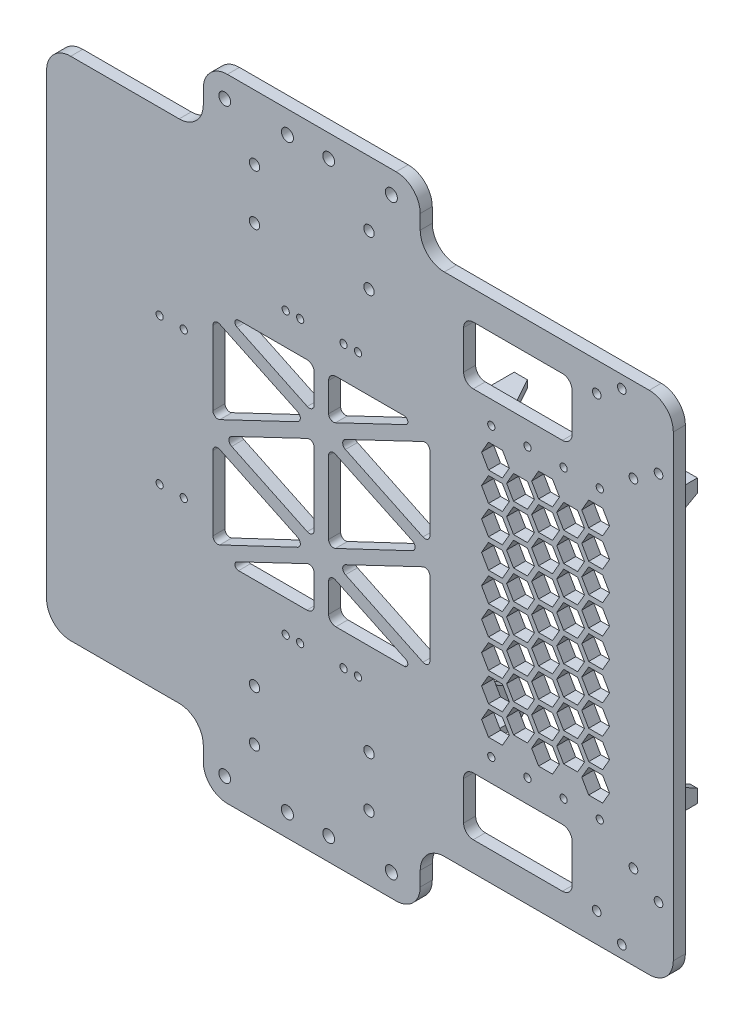
SolidWorks part; units mm, degrees
ref_plane "前视基准面" through (0, 0, 0) normal (0, 0, 1) x (1, 0, 0)
ref_plane "上视基准面" through (0, 0, 0) normal (0, 1, 0) x (1, 0, 0)
ref_plane "右视基准面" through (0, 0, 0) normal (1, 0, 0) x (0, 0, -1)
sketch "草图1" plane through (0, 0, 0) normal (0, 0, 1) x (1, 0, 0)
  line L2 (-130, 95) -> (-130, -95)
  line L3 (-120, -105) -> (-75, -105)
  line L4 (130, 95) -> (130, -95)
  line L5 (126.7518, 102.3765) -> (130, 105) construction
  line L6 (-130, -105) -> (-126.7518, -102.3765) construction
  line L9 (-65, -115) -> (-65, -121)
  line L10 (-55, -131) -> (15, -131)
  line L11 (25, -121) -> (25, -115)
  line L13 (35, -105) -> (120, -105)
  line L14 (126.7518, -102.3765) -> (130, -105) construction
  line L15 (-130, 105) -> (-126.7518, 102.3765) construction
  line L16 (-130, 0) -> (130, 0) construction
  line L17 (35, 105) -> (120, 105)
  line L18 (25, 121) -> (25, 115)
  line L19 (-55, 131) -> (15, 131)
  line L20 (-65, 115) -> (-65, 121)
  line L21 (-120, 105) -> (-75, 105)
  arc A1 (-120, -105) -> (-130, -95) centre (-120, -95) cw
  arc A3 (120, -105) -> (130, -95) centre (120, -95) ccw
  arc A8 (-65, -115) -> (-75, -105) centre (-75, -115) ccw
  arc A9 (25, -115) -> (35, -105) centre (35, -115) cw
  arc A10 (-55, -131) -> (-65, -121) centre (-55, -121) cw
  arc A11 (15, -131) -> (25, -121) centre (15, -121) ccw
  arc A12 (15, 131) -> (25, 121) centre (15, 121) cw
  arc A13 (-55, 131) -> (-65, 121) centre (-55, 121) ccw
  arc A14 (25, 115) -> (35, 105) centre (35, 115) ccw
  arc A15 (-65, 115) -> (-75, 105) centre (-75, 115) cw
  arc A16 (120, 105) -> (130, 95) centre (120, 95) cw
  arc A17 (-120, 105) -> (-130, 95) centre (-120, 95) ccw
  point P0 (0, 0)
  point P40 (25, -105)
  point P45 (25, 105)
  dimension "D2" = 10
  dimension "D3" = 65
  dimension "D4" = 10
  dimension "D5" = 105
  dimension "D7" = 10
  dimension "D8" = 10
  dimension "D10" = 10
  dimension "D12" = 10
  dimension "D13" = 105
  dimension "D18" = 90
  dimension "D19" = 6
extrude "凸台-拉伸1" add sketch "草图1" along normal blind 5
sketch "草图4" plane through (0, 0, 0) normal (0, 0, -1) x (-1, 0, 0)
  line L0 (-39, -47.5) -> (-39, -58.5)
  line L1 (-39, -58.5) -> (-50, -58.5)
  line L2 (-50, -58.5) -> (-50, -55.5)
  line L3 (-50, -55.5) -> (-42, -55.5)
  line L4 (-42, -55.5) -> (-42, -47.5)
  line L5 (-42, -47.5) -> (-39, -47.5)
  line L6 (-130, 0) -> (-25.5592, 0) construction
  line L7 (-130, -95) -> (-130, 95) construction
  line L10 (-130, -95) -> (-130, 95) construction
  dimension "D1" = 11
  dimension "D2" = 11
  dimension "D3" = 3
  dimension "D4" = 3
  dimension "D5" = 80
  dimension "D7" = 55.5
extrude "凸台-拉伸2" add sketch "草图4" along normal blind 20
sketch "草图5" plane through (0, -58.5, 0) normal (0, -1, 0) x (1, 0, 0)
  line L0 (50, -10) -> (44.5, -20)
  line L1 (50, -20) -> (50, 0) construction
  line L2 (50, -20) -> (39, -20) construction
  line L3 (44.5, -20) -> (50, -20)
  line L4 (50, -20) -> (50, -10)
  dimension "D1" = 10
  dimension "D2" = 5.5
extrude "切除-拉伸3" cut sketch "草图5" against normal blind 10
sketch "草图6" plane through (39, 0, 0) normal (-1, 0, 0) x (0, 0, 1)
  line L0 (-20, -53) -> (-10, -47.5)
  line L1 (-20, -58.5) -> (-20, -47.5) construction
  line L2 (-20, -47.5) -> (0, -47.5) construction
  line L3 (-10, -47.5) -> (-20, -47.5)
  line L4 (-20, -47.5) -> (-20, -53)
  dimension "D1" = 10
  dimension "D2" = 5.5
extrude "切除-拉伸4" cut sketch "草图6" against normal blind 10
ref_plane "基准面2" through (77, 0, 0) normal (1, 0, 0) x (0, 0, -1)
mirror "镜向1" about plane through (77, 0, 0) normal (1, 0, 0) of "凸台-拉伸2", "切除-拉伸4", "切除-拉伸3"
mirror "镜向2" about plane through (0, 0, 0) normal (0, 1, 0) of "镜向1"
sketch "草图7" plane through (0, 0, 0) normal (0, 0, -1) x (-1, 0, 0)
  line L4 (-112, -55.5) -> (-104, -55.5) construction
  line L5 (-112, 47.5) -> (-112, 55.5) construction
  line L6 (-112, 55.5) -> (-104, 55.5) construction
  line L7 (-92.013, 36) -> (-94.8997, 41)
  line L8 (-94.8997, 41) -> (-100.6732, 41)
  line L9 (-100.6732, 41) -> (-103.56, 36)
  line L10 (-103.56, 36) -> (-100.6732, 31)
  line L11 (-100.6732, 31) -> (-94.8997, 31)
  line L12 (-94.8997, 31) -> (-92.013, 36)
  line L13 (-77.0019, 36) -> (-97.7865, 36) construction
  line L14 (-74.1151, 31) -> (-71.2284, 36)
  line L15 (-71.2284, 36) -> (-74.1151, 41)
  line L16 (-74.1151, 41) -> (-79.8886, 41)
  line L17 (-79.8886, 41) -> (-82.7754, 36)
  line L18 (-82.7754, 36) -> (-79.8886, 31)
  line L19 (-79.8886, 31) -> (-74.1151, 31)
  line L20 (-92.013, 24) -> (-94.8997, 29)
  line L21 (-93.1677, 30) -> (-90.2809, 25)
  line L22 (-90.2809, 25) -> (-84.5074, 25)
  line L23 (-84.5074, 25) -> (-81.6207, 30)
  line L24 (-81.6207, 30) -> (-84.5074, 35)
  line L25 (-84.5074, 35) -> (-90.2809, 35)
  line L26 (-90.2809, 35) -> (-93.1677, 30)
  line L27 (-84.5074, 37) -> (-81.6207, 42)
  line L28 (-81.6207, 42) -> (-84.5074, 47)
  line L29 (-84.5074, 47) -> (-90.2809, 47)
  line L30 (-90.2809, 47) -> (-93.1677, 42)
  line L31 (-93.1677, 42) -> (-90.2809, 37)
  line L32 (-90.2809, 37) -> (-84.5074, 37)
  line L33 (-79.8886, 43) -> (-74.1151, 43)
  line L34 (-74.1151, 43) -> (-71.2284, 48)
  line L35 (-71.2284, 48) -> (-74.1151, 53)
  line L36 (-74.1151, 53) -> (-79.8886, 53)
  line L37 (-79.8886, 53) -> (-82.7754, 48)
  line L38 (-82.7754, 48) -> (-79.8886, 43)
  line L39 (-94.8997, 43) -> (-92.013, 48)
  line L40 (-92.013, 48) -> (-94.8997, 53)
  line L41 (-94.8997, 53) -> (-100.6732, 53)
  line L42 (-100.6732, 53) -> (-103.56, 48)
  line L43 (-103.56, 48) -> (-100.6732, 43)
  line L44 (-100.6732, 43) -> (-94.8997, 43)
  line L45 (-72.3831, 42) -> (-69.4963, 37)
  line L46 (-69.4963, 37) -> (-63.7228, 37)
  line L47 (-63.7228, 37) -> (-60.8361, 42)
  line L48 (-60.8361, 42) -> (-63.7228, 47)
  line L49 (-63.7228, 47) -> (-69.4963, 47)
  line L50 (-69.4963, 47) -> (-72.3831, 42)
  line L51 (-94.8997, 29) -> (-100.6732, 29)
  line L52 (-100.6732, 29) -> (-103.56, 24)
  line L53 (-103.56, 24) -> (-100.6732, 19)
  line L54 (-100.6732, 19) -> (-94.8997, 19)
  line L55 (-94.8997, 19) -> (-92.013, 24)
  line L56 (-93.1677, 18) -> (-90.2809, 13)
  line L57 (-90.2809, 13) -> (-84.5074, 13)
  line L58 (-84.5074, 13) -> (-81.6207, 18)
  line L59 (-81.6207, 18) -> (-84.5074, 23)
  line L60 (-84.5074, 23) -> (-90.2809, 23)
  line L61 (-90.2809, 23) -> (-93.1677, 18)
  line L62 (-74.1151, 19) -> (-71.2284, 24)
  line L63 (-71.2284, 24) -> (-74.1151, 29)
  line L64 (-74.1151, 29) -> (-79.8886, 29)
  line L65 (-79.8886, 29) -> (-82.7754, 24)
  line L66 (-82.7754, 24) -> (-79.8886, 19)
  line L67 (-79.8886, 19) -> (-74.1151, 19)
  line L68 (-72.3831, 30) -> (-69.4963, 25)
  line L69 (-69.4963, 25) -> (-63.7228, 25)
  line L70 (-63.7228, 25) -> (-60.8361, 30)
  line L71 (-60.8361, 30) -> (-63.7228, 35)
  line L72 (-63.7228, 35) -> (-69.4963, 35)
  line L73 (-69.4963, 35) -> (-72.3831, 30)
  line L74 (-92.013, 12) -> (-94.8997, 17)
  line L75 (-94.8997, 17) -> (-100.6732, 17)
  line L76 (-100.6732, 17) -> (-103.56, 12)
  line L77 (-103.56, 12) -> (-100.6732, 7)
  line L78 (-100.6732, 7) -> (-94.8997, 7)
  line L79 (-94.8997, 7) -> (-92.013, 12)
  line L80 (-93.1677, 6) -> (-90.2809, 1)
  line L81 (-90.2809, 1) -> (-84.5074, 1)
  line L82 (-84.5074, 1) -> (-81.6207, 6)
  line L83 (-81.6207, 6) -> (-84.5074, 11)
  line L84 (-84.5074, 11) -> (-90.2809, 11)
  line L85 (-90.2809, 11) -> (-93.1677, 6)
  line L86 (-74.1151, 7) -> (-71.2284, 12)
  line L87 (-71.2284, 12) -> (-74.1151, 17)
  line L88 (-74.1151, 17) -> (-79.8886, 17)
  line L89 (-79.8886, 17) -> (-82.7754, 12)
  line L90 (-82.7754, 12) -> (-79.8886, 7)
  line L91 (-79.8886, 7) -> (-74.1151, 7)
  line L92 (-72.3831, 18) -> (-69.4963, 13)
  line L93 (-69.4963, 13) -> (-63.7228, 13)
  line L94 (-63.7228, 13) -> (-60.8361, 18)
  line L95 (-60.8361, 18) -> (-63.7228, 23)
  line L96 (-63.7228, 23) -> (-69.4963, 23)
  line L97 (-69.4963, 23) -> (-72.3831, 18)
  line L98 (-92.013, 0) -> (-94.8997, 5)
  line L99 (-94.8997, 5) -> (-100.6732, 5)
  line L100 (-100.6732, 5) -> (-103.56, 0)
  line L101 (-103.56, 0) -> (-100.6732, -5)
  line L102 (-100.6732, -5) -> (-94.8997, -5)
  line L103 (-94.8997, -5) -> (-92.013, 0)
  line L104 (-93.1677, -6) -> (-90.2809, -11)
  line L105 (-90.2809, -11) -> (-84.5074, -11)
  line L106 (-84.5074, -11) -> (-81.6207, -6)
  line L107 (-81.6207, -6) -> (-84.5074, -1)
  line L108 (-84.5074, -1) -> (-90.2809, -1)
  line L109 (-90.2809, -1) -> (-93.1677, -6)
  line L110 (-74.1151, -5) -> (-71.2284, 0)
  line L111 (-71.2284, 0) -> (-74.1151, 5)
  line L112 (-74.1151, 5) -> (-79.8886, 5)
  line L113 (-79.8886, 5) -> (-82.7754, 0)
  line L114 (-82.7754, 0) -> (-79.8886, -5)
  line L115 (-79.8886, -5) -> (-74.1151, -5)
  line L116 (-72.3831, 6) -> (-69.4963, 1)
  line L117 (-69.4963, 1) -> (-63.7228, 1)
  line L118 (-63.7228, 1) -> (-60.8361, 6)
  line L119 (-60.8361, 6) -> (-63.7228, 11)
  line L120 (-63.7228, 11) -> (-69.4963, 11)
  line L121 (-69.4963, 11) -> (-72.3831, 6)
  line L122 (-92.013, -12) -> (-94.8997, -7)
  line L123 (-94.8997, -7) -> (-100.6732, -7)
  line L124 (-100.6732, -7) -> (-103.56, -12)
  line L125 (-103.56, -12) -> (-100.6732, -17)
  line L126 (-100.6732, -17) -> (-94.8997, -17)
  line L127 (-94.8997, -17) -> (-92.013, -12)
  line L128 (-93.1677, -18) -> (-90.2809, -23)
  line L129 (-90.2809, -23) -> (-84.5074, -23)
  line L130 (-84.5074, -23) -> (-81.6207, -18)
  line L131 (-81.6207, -18) -> (-84.5074, -13)
  line L132 (-84.5074, -13) -> (-90.2809, -13)
  line L133 (-90.2809, -13) -> (-93.1677, -18)
  line L134 (-74.1151, -17) -> (-71.2284, -12)
  line L135 (-71.2284, -12) -> (-74.1151, -7)
  line L136 (-74.1151, -7) -> (-79.8886, -7)
  line L137 (-79.8886, -7) -> (-82.7754, -12)
  line L138 (-82.7754, -12) -> (-79.8886, -17)
  line L139 (-79.8886, -17) -> (-74.1151, -17)
  line L140 (-72.3831, -6) -> (-69.4963, -11)
  line L141 (-69.4963, -11) -> (-63.7228, -11)
  line L142 (-63.7228, -11) -> (-60.8361, -6)
  line L143 (-60.8361, -6) -> (-63.7228, -1)
  line L144 (-63.7228, -1) -> (-69.4963, -1)
  line L145 (-69.4963, -1) -> (-72.3831, -6)
  line L146 (-92.013, -24) -> (-94.8997, -19)
  line L147 (-94.8997, -19) -> (-100.6732, -19)
  line L148 (-100.6732, -19) -> (-103.56, -24)
  line L149 (-103.56, -24) -> (-100.6732, -29)
  line L150 (-100.6732, -29) -> (-94.8997, -29)
  line L151 (-94.8997, -29) -> (-92.013, -24)
  line L152 (-93.1677, -30) -> (-90.2809, -35)
  line L153 (-90.2809, -35) -> (-84.5074, -35)
  line L154 (-84.5074, -35) -> (-81.6207, -30)
  line L155 (-81.6207, -30) -> (-84.5074, -25)
  line L156 (-84.5074, -25) -> (-90.2809, -25)
  line L157 (-90.2809, -25) -> (-93.1677, -30)
  line L158 (-74.1151, -29) -> (-71.2284, -24)
  line L159 (-71.2284, -24) -> (-74.1151, -19)
  line L160 (-74.1151, -19) -> (-79.8886, -19)
  line L161 (-79.8886, -19) -> (-82.7754, -24)
  line L162 (-82.7754, -24) -> (-79.8886, -29)
  line L163 (-79.8886, -29) -> (-74.1151, -29)
  line L164 (-72.3831, -18) -> (-69.4963, -23)
  line L165 (-69.4963, -23) -> (-63.7228, -23)
  line L166 (-63.7228, -23) -> (-60.8361, -18)
  line L167 (-60.8361, -18) -> (-63.7228, -13)
  line L168 (-63.7228, -13) -> (-69.4963, -13)
  line L169 (-69.4963, -13) -> (-72.3831, -18)
  line L170 (-92.013, -36) -> (-94.8997, -31)
  line L171 (-94.8997, -31) -> (-100.6732, -31)
  line L172 (-100.6732, -31) -> (-103.56, -36)
  line L173 (-103.56, -36) -> (-100.6732, -41)
  line L174 (-100.6732, -41) -> (-94.8997, -41)
  line L175 (-94.8997, -41) -> (-92.013, -36)
  line L176 (-93.1677, -42) -> (-90.2809, -47)
  line L177 (-90.2809, -47) -> (-84.5074, -47)
  line L178 (-84.5074, -47) -> (-81.6207, -42)
  line L179 (-81.6207, -42) -> (-84.5074, -37)
  line L180 (-84.5074, -37) -> (-90.2809, -37)
  line L181 (-90.2809, -37) -> (-93.1677, -42)
  line L182 (-74.1151, -41) -> (-71.2284, -36)
  line L183 (-71.2284, -36) -> (-74.1151, -31)
  line L184 (-74.1151, -31) -> (-79.8886, -31)
  line L185 (-79.8886, -31) -> (-82.7754, -36)
  line L186 (-82.7754, -36) -> (-79.8886, -41)
  line L187 (-79.8886, -41) -> (-74.1151, -41)
  line L188 (-72.3831, -30) -> (-69.4963, -35)
  line L189 (-69.4963, -35) -> (-63.7228, -35)
  line L190 (-63.7228, -35) -> (-60.8361, -30)
  line L191 (-60.8361, -30) -> (-63.7228, -25)
  line L192 (-63.7228, -25) -> (-69.4963, -25)
  line L193 (-69.4963, -25) -> (-72.3831, -30)
  line L194 (-92.013, -48) -> (-94.8997, -43)
  line L195 (-94.8997, -43) -> (-100.6732, -43)
  line L196 (-100.6732, -43) -> (-103.56, -48)
  line L197 (-103.56, -48) -> (-100.6732, -53)
  line L198 (-100.6732, -53) -> (-94.8997, -53)
  line L199 (-94.8997, -53) -> (-92.013, -48)
  line L206 (-74.1151, -53) -> (-71.2284, -48)
  line L207 (-71.2284, -48) -> (-74.1151, -43)
  line L208 (-74.1151, -43) -> (-79.8886, -43)
  line L209 (-79.8886, -43) -> (-82.7754, -48)
  line L210 (-82.7754, -48) -> (-79.8886, -53)
  line L211 (-79.8886, -53) -> (-74.1151, -53)
  line L212 (-72.3831, -42) -> (-69.4963, -47)
  line L213 (-69.4963, -47) -> (-63.7228, -47)
  line L214 (-63.7228, -47) -> (-60.8361, -42)
  line L215 (-60.8361, -42) -> (-63.7228, -37)
  line L216 (-63.7228, -37) -> (-69.4963, -37)
  line L217 (-69.4963, -37) -> (-72.3831, -42)
  line L218 (-61.9908, 36) -> (-59.104, 31)
  line L219 (-61.9908, 48) -> (-59.104, 43)
  line L220 (-59.104, 43) -> (-53.3305, 43)
  line L221 (-53.3305, 43) -> (-50.4438, 48)
  line L222 (-50.4438, 48) -> (-53.3305, 53)
  line L223 (-53.3305, 53) -> (-59.104, 53)
  line L224 (-59.104, 53) -> (-61.9908, 48)
  line L225 (-59.104, 31) -> (-53.3305, 31)
  line L226 (-53.3305, 31) -> (-50.4438, 36)
  line L227 (-50.4438, 36) -> (-53.3305, 41)
  line L228 (-53.3305, 41) -> (-59.104, 41)
  line L229 (-59.104, 41) -> (-61.9908, 36)
  line L230 (-61.9908, 24) -> (-59.104, 19)
  line L231 (-59.104, 19) -> (-53.3305, 19)
  line L232 (-53.3305, 19) -> (-50.4438, 24)
  line L233 (-50.4438, 24) -> (-53.3305, 29)
  line L234 (-53.3305, 29) -> (-59.104, 29)
  line L235 (-59.104, 29) -> (-61.9908, 24)
  line L236 (-61.9908, 12) -> (-59.104, 7)
  line L237 (-59.104, 7) -> (-53.3305, 7)
  line L238 (-53.3305, 7) -> (-50.4438, 12)
  line L239 (-50.4438, 12) -> (-53.3305, 17)
  line L240 (-53.3305, 17) -> (-59.104, 17)
  line L241 (-59.104, 17) -> (-61.9908, 12)
  line L242 (-61.9908, 0) -> (-59.104, -5)
  line L243 (-59.104, -5) -> (-53.3305, -5)
  line L244 (-53.3305, -5) -> (-50.4438, 0)
  line L245 (-50.4438, 0) -> (-53.3305, 5)
  line L246 (-53.3305, 5) -> (-59.104, 5)
  line L247 (-59.104, 5) -> (-61.9908, 0)
  line L248 (-61.9908, -12) -> (-59.104, -17)
  line L249 (-59.104, -17) -> (-53.3305, -17)
  line L250 (-53.3305, -17) -> (-50.4438, -12)
  line L251 (-50.4438, -12) -> (-53.3305, -7)
  line L252 (-53.3305, -7) -> (-59.104, -7)
  line L253 (-59.104, -7) -> (-61.9908, -12)
  line L254 (-61.9908, -24) -> (-59.104, -29)
  line L255 (-59.104, -29) -> (-53.3305, -29)
  line L256 (-53.3305, -29) -> (-50.4438, -24)
  line L257 (-50.4438, -24) -> (-53.3305, -19)
  line L258 (-53.3305, -19) -> (-59.104, -19)
  line L259 (-59.104, -19) -> (-61.9908, -24)
  line L260 (-61.9908, -36) -> (-59.104, -41)
  line L261 (-59.104, -41) -> (-53.3305, -41)
  line L262 (-53.3305, -41) -> (-50.4438, -36)
  line L263 (-50.4438, -36) -> (-53.3305, -31)
  line L264 (-53.3305, -31) -> (-59.104, -31)
  line L265 (-59.104, -31) -> (-61.9908, -36)
  line L266 (-61.9908, -48) -> (-59.104, -53)
  line L267 (-59.104, -53) -> (-53.3305, -53)
  line L268 (-53.3305, -53) -> (-50.4438, -48)
  line L269 (-50.4438, -48) -> (-53.3305, -43)
  line L270 (-53.3305, -43) -> (-59.104, -43)
  line L271 (-59.104, -43) -> (-61.9908, -48)
  line L272 (-93.1677, -54) -> (-90.2809, -59) [skipped]
  line L273 (-90.2809, -59) -> (-84.5074, -59) [skipped]
  line L274 (-84.5074, -59) -> (-81.6207, -54) [skipped]
  line L275 (-81.6207, -54) -> (-84.5074, -49) [skipped]
  line L276 (-84.5074, -49) -> (-90.2809, -49) [skipped]
  line L277 (-90.2809, -49) -> (-93.1677, -54) [skipped]
  circle A0 centre (-97.7865, 36) radius 5 construction
  circle A1 centre (-77.0019, 36) radius 5 construction
  circle A2 centre (-87.3942, 30) radius 5 construction
  circle A3 centre (-87.3942, 42) radius 5 construction
  circle A4 centre (-77.0019, 48) radius 5 construction
  circle A5 centre (-97.7865, 48) radius 5 construction
  circle A6 centre (-66.6096, 42) radius 5 construction
  circle A7 centre (-56.2173, 48) radius 5 construction
  point P4 (-87.3942, 37)
  dimension "D1" = 2
  dimension "D3" = 10
  dimension "D4" = 10
  dimension "D5" = 2
  dimension "D7" = 10
  dimension "D11" = 10
  dimension "D14" = 10
  dimension "D15" = 10
  dimension "D20" = 10
  dimension "D2" = 2
  dimension "D6" = 2
  dimension "D8" = 2
  dimension "D9" = 2
  dimension "D10" = 2
  dimension "D12" = 2
  dimension "D13" = 2
  dimension "D16" = 2
  dimension "D17" = 2
  dimension "D19" = 2
  dimension "D21" = 9
  dimension "D22" = 2.5
  dimension "D23" = 2.5
  dimension "D24" = 8.44
  dimension "D18" = 8
extrude "切除-拉伸5" cut sketch "草图7" against normal blind 5
sketch "草图8" plane through (0, 0, 0) normal (0, 0, -1) x (-1, 0, 0)
  line L0 (-75.3677, 120) -> (-75.3677, -120)
  line L1 (-100.0285, 77.2863) -> (-100.0285, -77.2863)
  line L2 (-100.0285, 77.2863) -> (-75.3677, 120)
  line L3 (-100.0285, -77.2863) -> (-75.3677, -120)
  line L4 (-37.1297, 0) -> (-146.8562, 0) construction
  dimension "D1" = 30
  dimension "D2" = 30
  dimension "D3" = 120
  dimension "D4" = 120
sketch "草图9" plane through (0, 0, 0) normal (0, 0, -1) x (-1, 0, 0)
  line L0 (148.8518, 0) -> (-37.1297, 0) construction
  line L1 (-29, 41) -> (-29, 4)
  line L2 (-25, -45) -> (13, -45)
  line L3 (61, -41) -> (61, -4)
  line L4 (57, 45) -> (19, 45)
  line L14 (-29, 41) -> (9.8049, 22.5)
  line L15 (57, 0) -> (19, -18.1163)
  line L16 (130, 95) -> (130, -95) construction
  line L17 (63, 93) -> (118, 93)
  line L18 (63, 93) -> (63, 66)
  line L19 (63, 66) -> (118, 66)
  line L20 (118, 93) -> (118, 66)
  line L21 (75, 105) -> (120, 105) construction
  line L22 (63, -66) -> (118, -66)
  line L23 (118, -93) -> (118, -66)
  line L24 (63, -93) -> (118, -93)
  line L25 (63, -93) -> (63, -66)
  line L26 (-120, 105) -> (-35, 105) construction
  line L27 (-43, 93) -> (-88, 93)
  line L28 (-43, 93) -> (-43, 69)
  line L29 (-43, 69) -> (-88, 69)
  line L30 (-88, 93) -> (-88, 69)
  line L31 (-130, -95) -> (-130, 95) construction
  line L32 (-43, -69) -> (-88, -69)
  line L33 (-88, -93) -> (-88, -69)
  line L34 (-43, -93) -> (-88, -93)
  line L35 (-43, -93) -> (-43, -69)
  line L36 (-25, 45) -> (13, 26.8837)
  line L37 (-25, -45) -> (13, -26.8837)
  line L38 (61, 41) -> (22.0746, 22.5575)
  line L39 (-25.5359, 0) -> (13, -18.258)
  line L40 (57, 45) -> (19, 26.8837)
  line L41 (57, -45) -> (19, -26.8837)
  line L42 (16, 61.4977) -> (16, -60.5731) construction
  line L43 (13, 45) -> (13, 26.8837)
  line L44 (19, 45) -> (19, 26.8837)
  line L45 (13, 18.258) -> (13, -18.258)
  line L46 (9.8049, 22.5) -> (-29, 4)
  line L47 (19, 18.1163) -> (57, 0)
  line L48 (22.0746, 22.5575) -> (61, 4)
  line L49 (13, 18.258) -> (-25.5359, 0)
  line L50 (19, 18.1163) -> (19, -18.1163)
  line L51 (22.0746, -22.5575) -> (61, -41)
  line L52 (9.8049, -22.5) -> (-29, -41)
  line L53 (9.8049, -22.5) -> (-29, -4)
  line L54 (22.0746, -22.5575) -> (61, -4)
  line L55 (13, -26.8837) -> (13, -45)
  line L56 (19, -26.8837) -> (19, -45)
  line L57 (13, 45) -> (-25, 45)
  line L58 (-29, -4) -> (-29, -41)
  line L59 (19, -45) -> (57, -45)
  line L60 (61, 4) -> (61, 41)
  line L61 (-44, 41) -> (-44, -37.8122) construction
  dimension "D1" = 45
  dimension "D2" = 45
  dimension "D3" = 15
  dimension "D4" = 90
  dimension "D5" = 1
  dimension "D7" = 12
  dimension "D8" = 12
  dimension "D9" = 27
  dimension "D10" = 55
  dimension "D11" = 12
  dimension "D12" = 45
  dimension "D13" = 42
  dimension "D14" = 24
  dimension "D21" = 4
  dimension "D22" = 4
  dimension "D23" = 4
  dimension "D24" = 4
  dimension "D26" = 4
  dimension "D27" = 3
  dimension "D28" = 45
extrude "切除-拉伸6" cut sketch "草图9" against normal blind 5 contours L27 L30 L29 L28 | L34 L35 L32 L33 | L4 L44 L40 | L48 L60 L38 | L47 L50 L15 | L54 L51 L3 | L56 L59 L41 | L55 L37 L2 | L53 L58 L52 | L45 L49 L39 | L46 L14 L1 | L43 L57 L36 | L57 L36 L43 region at (16.065, 22.5, 0) region at (-0.3333, -38.9612, 0) region at (-48.0249, -22.5192, 0) region at (-31.6667, 38.9612, 0) region at (-31.6667, 0, 0) region at (65.5, 81, 0) region at (65.5, -81, 0) region at (-0.3333, 38.9612, 0) region at (-48.0249, 22.5192, 0) region at (-0.1547, 0, 0) region at (-31.6667, -38.9612, 0) region at (16.065, -22.5, 0)
fillet "圆角1" radius 4 8 edges at (43, -93, 2.5) (88, -69, 2.5) (43, -69, 2.5) (88, -93, 2.5) (88, 69, 2.5) (43, 69, 2.5) (43, 93, 2.5) (88, 93, 2.5)
fillet "圆角2" radius 1.5 4 edges at (25, -45, 2.5) (-57, -45, 2.5) (25, 45, 2.5) (-57, 45, 2.5)
fillet "圆角3" radius 2 22 edges at (29, -4, 2.5) (29, 4, 2.5) (-13, -18.258, 2.5) (-61, -41, 2.5) (-61, 4, 2.5) (-13, -26.8837, 2.5) (-13, 18.258, 2.5) (-61, -4, 2.5) (-22.0746, -22.5575, 2.5) (25.5359, 0, 2.5) (-22.0746, 22.5575, 2.5) (-61, 41, 2.5) (-19, 26.8837, 2.5) (-19, -26.8837, 2.5) (-19, -18.1163, 2.5) (29, -41, 2.5) (29, 41, 2.5) (-57, 0, 2.5) (-9.8049, -22.5, 2.5) (-13, 26.8837, 2.5) (-9.8049, 22.5, 2.5) (-19, 18.1163, 2.5)
fillet "圆角4" radius 3 4 edges at (-13, -45, 2.5) (-13, 45, 2.5) (-19, -45, 2.5) (-19, 45, 2.5)
sketch "草图10" plane through (0, 0, 0) normal (0, 0, -1) x (-1, 0, 0)
  line L0 (-37.1297, 0) -> (-146.8562, 0) construction
  line L1 (-37.1297, 0) -> (-146.8562, 0) construction
  circle A0 centre (-123.8743, 76.9597) radius 1.8 construction
  circle A1 centre (-113.4687, 70.0334) radius 1.8 construction
  circle A2 centre (-108.6364, 99.852) radius 1.8 construction
  circle A3 centre (-98.2308, 92.9256) radius 1.8 construction
  circle A11 centre (-13.0267, 121.679) radius 2.5 construction
  circle A12 centre (56.0941, 121.679) radius 2.45 construction
  circle A13 centre (30.0941, 121.679) radius 2.5 construction
  circle A14 centre (12.9733, 121.679) radius 2.45 construction
  circle A15 centre (-123.8743, 76.9597) radius 1.8
  circle A16 centre (-113.4687, 70.0334) radius 1.8
  circle A17 centre (-108.6364, 99.852) radius 1.8
  circle A18 centre (-98.2308, 92.9256) radius 1.8
  circle A26 centre (-13.0267, 121.679) radius 2.5
  circle A27 centre (56.0941, 121.679) radius 2.45
  circle A28 centre (30.0941, 121.679) radius 2.5
  circle A29 centre (12.9733, 121.679) radius 2.45
  circle A30 centre (12.9733, -121.679) radius 2.45
  circle A31 centre (30.0941, -121.679) radius 2.5
  circle A32 centre (56.0941, -121.679) radius 2.45
  circle A33 centre (-13.0267, -121.679) radius 2.5
  circle A41 centre (-98.2308, -92.9256) radius 1.8
  circle A42 centre (-108.6364, -99.852) radius 1.8
  circle A43 centre (-113.4687, -70.0334) radius 1.8
  circle A44 centre (-123.8743, -76.9597) radius 1.8
  circle A45 centre (-99.5, 59.5) radius 1.5 construction
  circle A46 centre (-84.5, 59.5) radius 1.5 construction
  circle A47 centre (-69.5, 59.5) radius 1.5 construction
  circle A48 centre (-54.5, 59.5) radius 1.5 construction
  circle A49 centre (0.8061, 58.25) radius 1.5 construction
  circle A50 centre (6.8061, 58.25) radius 1.5 construction
  circle A51 centre (24.8061, 58.25) radius 1.5 construction
  circle A52 centre (30.8061, 58.25) radius 1.5 construction
  circle A53 centre (-99.5, 59.5) radius 1.5
  circle A54 centre (-84.5, 59.5) radius 1.5
  circle A55 centre (-69.5, 59.5) radius 1.5
  circle A56 centre (-54.5, 59.5) radius 1.5
  circle A57 centre (0.8061, 58.25) radius 1.5
  circle A58 centre (6.8061, 58.25) radius 1.5
  circle A59 centre (24.8061, 58.25) radius 1.5
  circle A60 centre (30.8061, 58.25) radius 1.5
  circle A61 centre (30.8061, -58.25) radius 1.5
  circle A62 centre (24.8061, -58.25) radius 1.5
  circle A63 centre (6.8061, -58.25) radius 1.5
  circle A64 centre (0.8061, -58.25) radius 1.5
  circle A65 centre (-54.5, -59.5) radius 1.5
  circle A66 centre (-69.5, -59.5) radius 1.5
  circle A67 centre (-84.5, -59.5) radius 1.5
  circle A68 centre (-99.5, -59.5) radius 1.5
  circle A89 centre (73.1015, 30.3) radius 1.5 construction
  circle A90 centre (83.1015, 30.3) radius 1.5 construction
  circle A91 centre (73.1015, 30.3) radius 1.5
  circle A92 centre (83.1015, 30.3) radius 1.5
  circle A93 centre (83.1015, -30.3) radius 1.5
  circle A94 centre (73.1015, -30.3) radius 1.5
  circle A95 centre (43.75, 83.1665) radius 2.15 construction
  circle A96 centre (43.75, 104.1665) radius 2.15 construction
  circle A97 centre (-3.75, 83.1665) radius 2.15 construction
  circle A98 centre (-3.75, 104.1665) radius 2.15 construction
  circle A99 centre (43.75, 83.1665) radius 2.15
  circle A100 centre (43.75, 104.1665) radius 2.15
  circle A101 centre (-3.75, 83.1665) radius 2.15
  circle A102 centre (-3.75, 104.1665) radius 2.15
  circle A103 centre (-3.75, -104.1665) radius 2.15
  circle A104 centre (-3.75, -83.1665) radius 2.15
  circle A105 centre (43.75, -104.1665) radius 2.15
  circle A106 centre (43.75, -83.1665) radius 2.15
  point P64 (-3.75, 83.1665)
extrude "切除-拉伸7" cut sketch "草图10" against normal through all
equation "\"45、\"=43.7672"
